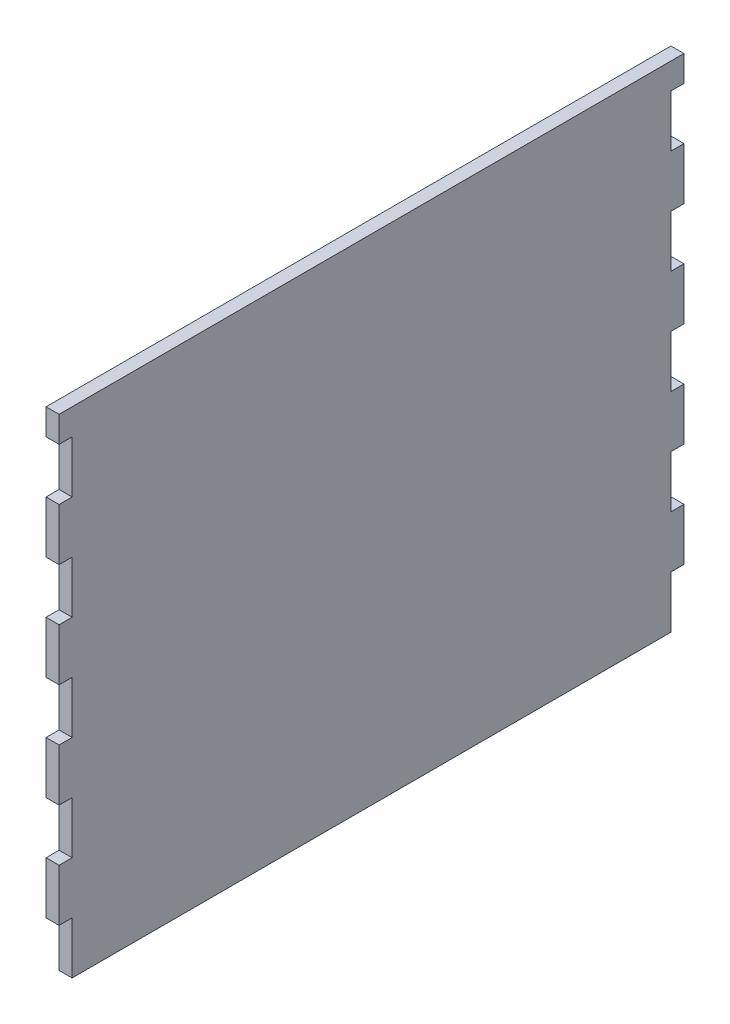
SolidWorks part; units mm, degrees
ref_plane "Front Plane" through (0, 0, 0) normal (0, 0, 1) x (1, 0, 0)
ref_plane "Top Plane" through (0, 0, 0) normal (0, 1, 0) x (1, 0, 0)
ref_plane "Right Plane" through (0, 0, 0) normal (1, 0, 0) x (0, 0, -1)
sketch "Sketch1" plane through (0, 0, 0) normal (1, 0, 0) x (0, 0, -1)
  line L25 (-326.0788, 150.6225) -> (-21.2788, 150.6225)
  line L26 (-326.0788, 150.6225) -> (-326.0788, -90.6775)
  line L27 (-326.0788, -90.6775) -> (-21.2788, -90.6775)
  line L28 (-21.2788, 150.6225) -> (-21.2788, -90.6775)
  dimension "D1" = 241.3
  dimension "D2" = 304.8
extrude "Boss-Extrude4" add sketch "Sketch1" along normal blind 6.35
sketch "Sketch2" plane through (6.35, 0, 0) normal (1, 0, 0) x (0, 0, -1)
  line L0 (-326.0788, 150.6225) -> (-326.0788, -90.6775) construction
  line L1 (-326.0788, -90.6775) -> (-319.7288, -90.6775)
  line L2 (-326.0788, -90.6775) -> (-326.0788, -65.2775)
  line L3 (-326.0788, -65.2775) -> (-319.7288, -65.2775)
  line L4 (-319.7288, -90.6775) -> (-319.7288, -65.2775)
  line L5 (-326.0788, -39.8775) -> (-319.7288, -39.8775)
  line L6 (-326.0788, -39.8775) -> (-326.0788, -14.4775)
  line L7 (-326.0788, -14.4775) -> (-319.7288, -14.4775)
  line L8 (-319.7288, -39.8775) -> (-319.7288, -14.4775)
  line L10 (-326.0788, 10.9225) -> (-319.7288, 10.9225)
  line L11 (-326.0788, 10.9225) -> (-326.0788, 36.3225)
  line L12 (-326.0788, 36.3225) -> (-319.7288, 36.3225)
  line L13 (-319.7288, 10.9225) -> (-319.7288, 36.3225)
  line L14 (-326.0788, 61.7225) -> (-319.7288, 61.7225)
  line L15 (-326.0788, 61.7225) -> (-326.0788, 87.1225)
  line L16 (-326.0788, 87.1225) -> (-319.7288, 87.1225)
  line L17 (-319.7288, 61.7225) -> (-319.7288, 87.1225)
  line L18 (-326.0788, 112.5225) -> (-319.7288, 112.5225)
  line L19 (-326.0788, 112.5225) -> (-326.0788, 137.9225)
  line L20 (-326.0788, 137.9225) -> (-319.7288, 137.9225)
  line L21 (-319.7288, 112.5225) -> (-319.7288, 137.9225)
  dimension "D1" = 6.35
  dimension "D2" = 25.4
  dimension "D3" = 25.4
  dimension "D4" = 25.4
  dimension "D5" = 25.4
  dimension "D6" = 25.4
  dimension "D7" = 25.4
  dimension "D8" = 25.4
  dimension "D9" = 25.4
  dimension "D10" = 25.4
extrude "Cut-Extrude3" cut sketch "Sketch2" against normal blind 7.62
sketch "Sketch3" plane through (0, 0, 0) normal (-1, 0, 0) x (0, 0, 1)
  line L1 (21.2788, -90.6775) -> (27.6288, -90.6775)
  line L2 (21.2788, -90.6775) -> (21.2788, -65.207)
  line L3 (21.2788, -65.207) -> (27.6288, -65.207)
  line L4 (27.6288, -90.6775) -> (27.6288, -65.207)
  line L9 (21.2788, -90.6775) -> (21.2788, 150.6225) construction
  line L22 (21.2788, -39.807) -> (27.6288, -39.807)
  line L23 (21.2788, -39.807) -> (21.2788, -14.407)
  line L24 (21.2788, -14.407) -> (27.6288, -14.407)
  line L25 (27.6288, -39.807) -> (27.6288, -14.407)
  line L27 (21.2788, 10.993) -> (27.6288, 10.993)
  line L28 (21.2788, 10.993) -> (21.2788, 36.393)
  line L29 (21.2788, 36.393) -> (27.6288, 36.393)
  line L30 (27.6288, 10.993) -> (27.6288, 36.393)
  line L31 (21.2788, 61.793) -> (27.6288, 61.793)
  line L32 (21.2788, 61.793) -> (21.2788, 87.193)
  line L33 (21.2788, 87.193) -> (27.6288, 87.193)
  line L34 (27.6288, 61.793) -> (27.6288, 87.193)
  line L35 (21.2788, 112.593) -> (27.6288, 112.593)
  line L36 (21.2788, 112.593) -> (21.2788, 137.993)
  line L37 (21.2788, 137.993) -> (27.6288, 137.993)
  line L38 (27.6288, 112.593) -> (27.6288, 137.993)
  dimension "D1" = 6.35
  dimension "D2" = 25.4
  dimension "D3" = 25.4
  dimension "D4" = 25.4
  dimension "D5" = 25.4
  dimension "D6" = 25.4
  dimension "D7" = 25.4
  dimension "D8" = 25.4
  dimension "D9" = 6.35
  dimension "D10" = 25.4
extrude "Cut-Extrude4" cut sketch "Sketch3" against normal blind 7.62
